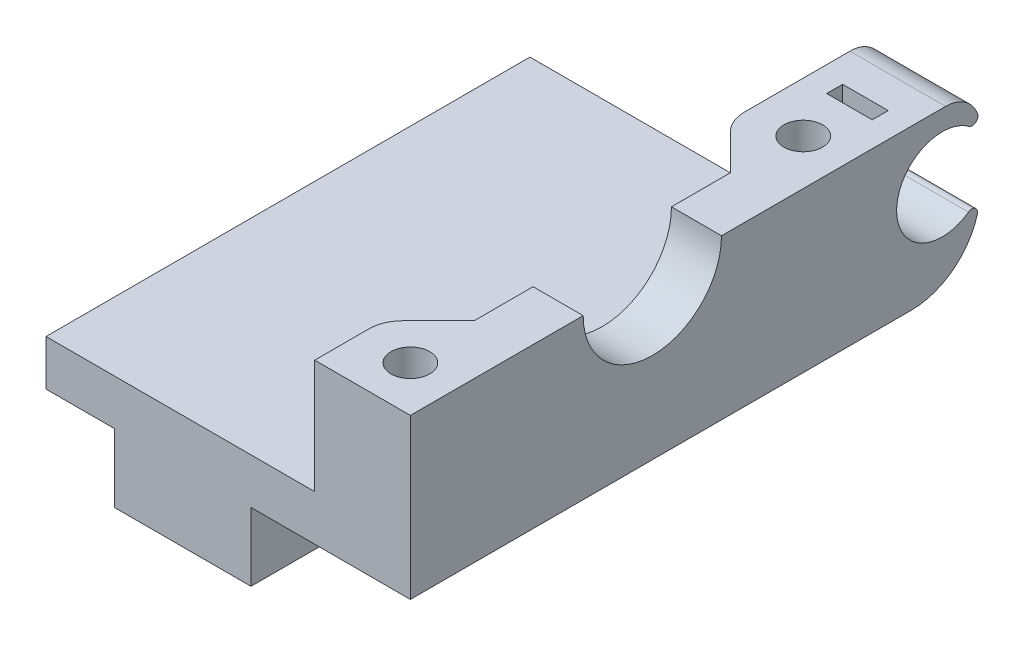
SolidWorks part; units mm, degrees
ref_plane "Plan de face" through (0, 0, 0) normal (0, 0, 1) x (1, 0, 0)
ref_plane "Plan de dessus" through (0, 0, 0) normal (0, 1, 0) x (1, 0, 0)
ref_plane "Plan de droite" through (0, 0, 0) normal (1, 0, 0) x (0, 0, -1)
sketch "Esquisse1" plane through (0, 0, 0) normal (0, 0, -1) x (1, 0, 0)
  line L0 (-1.3845, -46.2204) -> (38.6155, -46.2204)
  line L1 (38.6155, -46.2204) -> (38.6155, -42.2204)
  line L2 (38.6155, -42.2204) -> (24.6155, -42.2204)
  line L3 (24.6155, -42.2204) -> (24.6155, -36.2204)
  line L4 (24.6155, -36.2204) -> (12.6155, -36.2204)
  line L5 (12.6155, -36.2204) -> (12.6155, -42.2204)
  line L6 (12.6155, -42.2204) -> (-1.3845, -42.2204)
  line L7 (-1.3845, -42.2204) -> (-1.3845, -46.2204)
  dimension "D1" = 40
  dimension "D2" = 4
  dimension "D3" = 14
  dimension "D4" = 6
  dimension "D5" = 12
  dimension "D6" = 6
extrude "Boss.-Extru.1" add sketch "Esquisse1" along normal blind 42.5
hole_wizard "Dégagement M31" positions "Esquisse4" profile "Esquisse5" hole size "M3" standard "Din" end condition through all
sketch "Esquisse4" plane through (24.6155, 0, 0) normal (1, 0, 0) x (0, 0, -1)
  line L0 (0, 39.2204) -> (42.5, 39.2204) construction
  line L1 (0, 42.2204) -> (0, 36.2204) construction
  line L2 (42.5, 42.2204) -> (42.5, 36.2204) construction
  point P0 (10, 39.2204)
  point P2 (32.5, 39.2204)
  dimension "D1" = 10
  dimension "D2" = 10
sketch "Esquisse5" plane through (24.6155, 39.2204, -10) normal (0, 1, 0) x (0, 0, -1)
  line L0 (0, 0) -> (0, 26)
  line L1 (0, 26) -> (1.5, 26)
  line L2 (1.5, 26) -> (1.5, 0)
  line L5 (1.5, 0) -> (0, 0)
  line L11 (0, -6.35) -> (0, 107.95) construction
  dimension "Diamètre du perçage jusqu'au prochain" = 3
  dimension "Profondeur du perçage jusqu'au prochain" = 26
sketch "Esquisse10" plane through (0, 46.2204, 0) normal (0, 1, 0) x (1, 0, 0)
  line L0 (-1.3845, 0) -> (38.6155, 0) construction
  line L1 (34.2155, 0) -> (38.6155, 0)
  line L2 (34.2155, 0) -> (34.2155, 42.5)
  line L3 (34.2155, 42.5) -> (38.6155, 42.5)
  line L4 (38.6155, 0) -> (38.6155, 42.5)
  line L6 (34.2155, 42.5) -> (30.2155, 42.5)
  line L7 (34.2155, 42.5) -> (34.2155, 32.5)
  line L8 (34.2155, 32.5) -> (30.2155, 32.5)
  line L9 (30.2155, 42.5) -> (30.2155, 32.5)
  line L10 (34.2155, 0) -> (30.2155, 0)
  line L11 (34.2155, 0) -> (34.2155, 10)
  line L12 (34.2155, 10) -> (30.2155, 10)
  line L13 (30.2155, 0) -> (30.2155, 10)
  line M5 (-1.3845, 0) -> (38.6155, 0)
  line M6 (38.6155, 0) -> (38.6155, 42.5)
  line M7 (38.6155, 42.5) -> (-1.3845, 42.5)
  dimension "D1" = 4.4
  dimension "D2" = 4
  dimension "D3" = 10
  dimension "D4" = 4
  dimension "D5" = 10
extrude "Boss.-Extru.2" add sketch "Esquisse10" along normal blind 10 contours L9 L8 L2 M7 | L2 M5 M6 M7 | L13 L2 L12 M5 region at (36.4155, 46.2204, -21.25) region at (32.2155, 46.2204, -5) region at (32.2155, 46.2204, -37.5)
sketch "Esquisse12" plane through (38.6155, 0, 0) normal (1, 0, 0) x (0, 0, -1)
  line L1 (0, 56.2204) -> (42.5, 56.2204) construction
  circle A0 centre (21.25, 56.2204) radius 6.075
  dimension "D1" = 12.15
extrude "Enlèv. mat.-Extru.3" cut sketch "Esquisse12" against normal through all
hole_wizard "Dégagement M33" positions "Esquisse7" profile "Esquisse8" hole size "M3" standard "Din" end condition through all
sketch "Esquisse7" plane through (0, 42.2204, 0) normal (0, -1, 0) x (-1, 0, 0)
  line L1 (-34.6155, 38.5) -> (-2.6155, 38.5) construction
  line L2 (-34.6155, 38.5) -> (-34.6155, 4) construction
  line L3 (-34.6155, 4) -> (-2.6155, 4) construction
  line L4 (-2.6155, 38.5) -> (-2.6155, 4) construction
  line L5 (-24.6155, 42.5) -> (-12.6155, 42.5) construction
  line L6 (1.3845, 42.5) -> (1.3845, 0) construction
  line L7 (-38.6155, 42.5) -> (-38.6155, 0) construction
  point P0 (3, -59.9463)
  point P1 (-34.6155, 38.5)
  point P3 (-2.6155, 38.5)
  point P5 (-2.6155, 4)
  point P7 (-34.6155, 4)
  dimension "D1" = 4
  dimension "D2" = 4
  dimension "D3" = 4
  dimension "D4" = 4
sketch "Esquisse8" plane through (-3, 42.2204, 59.9463) normal (1, 0, 0) x (0, 0, -1)
  line L0 (0, 0) -> (0, 14)
  line L1 (0, 14) -> (1.7, 14)
  line L2 (1.7, 14) -> (1.7, 0)
  line L5 (1.7, 0) -> (0, 0)
  line L11 (0, -6.35) -> (0, 107.95) construction
  dimension "Diamètre du perçage jusqu'au prochain" = 3.4
  dimension "Profondeur du perçage jusqu'au prochain" = 14
sketch "Esquisse9" plane through (0, 42.2204, 0) normal (0, -1, 0) x (1, 0, 0)
  line L1 (32.8655, -35.4689) -> (31.1155, -38.5)
  line L2 (31.1155, -38.5) -> (32.8655, -41.5311)
  line L3 (32.8655, -41.5311) -> (36.3655, -41.5311)
  line L4 (36.3655, -41.5311) -> (38.1155, -38.5)
  line L5 (38.1155, -38.5) -> (36.3655, -35.4689)
  line L6 (36.3655, -35.4689) -> (32.8655, -35.4689)
  line L7 (4.3655, -35.4689) -> (0.8655, -35.4689)
  line L8 (0.8655, -35.4689) -> (-0.8845, -38.5)
  line L9 (-0.8845, -38.5) -> (0.8655, -41.5311)
  line L10 (0.8655, -41.5311) -> (4.3655, -41.5311)
  line L11 (4.3655, -41.5311) -> (6.1155, -38.5)
  line L12 (6.1155, -38.5) -> (4.3655, -35.4689)
  line L13 (32.8655, -0.9689) -> (31.1155, -4)
  line L14 (31.1155, -4) -> (32.8655, -7.0311)
  line L15 (32.8655, -7.0311) -> (36.3655, -7.0311)
  line L16 (36.3655, -7.0311) -> (38.1155, -4)
  line L17 (38.1155, -4) -> (36.3655, -0.9689)
  line L18 (36.3655, -0.9689) -> (32.8655, -0.9689)
  line L19 (4.3655, -0.9689) -> (0.8655, -0.9689)
  line L20 (0.8655, -0.9689) -> (-0.8845, -4)
  line L21 (-0.8845, -4) -> (0.8655, -7.0311)
  line L22 (0.8655, -7.0311) -> (4.3655, -7.0311)
  line L23 (4.3655, -7.0311) -> (6.1155, -4)
  line L24 (6.1155, -4) -> (4.3655, -0.9689)
  circle A0 centre (34.6155, -38.5) radius 3.0311 construction
  circle A1 centre (2.6155, -38.5) radius 3.0311 construction
  circle A2 centre (34.6155, -4) radius 3.0311 construction
  circle A3 centre (2.6155, -4) radius 3.0311 construction
  dimension "D1" = 3.5
extrude "Enlèv. mat.-Extru.1" cut sketch "Esquisse9" against normal blind 1.5
chamfer "Chanfrein1" distance 4 angle 45 2 edges at (30.2155, 51.2204, -32.5) (30.2155, 51.2204, -10)
sketch "Esquisse13" plane through (0, 0, -42.5) normal (0, 0, -1) x (-1, 0, 0)
  line L0 (-12.6155, 42.2204) -> (1.3845, 42.2204) construction
  line L1 (1.3845, 46.2204) -> (-6.6155, 46.2204)
  line L2 (1.3845, 46.2204) -> (1.3845, 42.2204)
  line L3 (1.3845, 42.2204) -> (-6.6155, 42.2204)
  line L4 (-6.6155, 46.2204) -> (-6.6155, 42.2204)
  line L5 (-12.6155, 36.2204) -> (-12.6155, 42.2204) construction
  dimension "D1" = 6
extrude "Enlèv. mat.-Extru.4" cut sketch "Esquisse13" against normal through all
sketch "Esquisse14" plane through (0, 0, -42.5) normal (0, 0, -1) x (-1, 0, 0)
  line L1 (-30.2155, 56.2204) -> (-38.6155, 56.2204)
  line L2 (-30.2155, 56.2204) -> (-30.2155, 42.2204)
  line L3 (-30.2155, 42.2204) -> (-38.6155, 42.2204)
  line L4 (-38.6155, 56.2204) -> (-38.6155, 42.2204)
extrude "Boss.-Extru.3" add sketch "Esquisse14" along normal blind 7.5
sketch "Esquisse15" plane through (30.2155, 0, 0) normal (-1, 0, 0) x (0, 0, 1)
  line L0 (-50, 42.2204) -> (-50, 56.2204) construction
  circle A0 centre (-46.7, 50.4385) radius 4
  dimension "D1" = 8
  dimension "D2" = 3.3
extrude "Enlèv. mat.-Extru.5" cut sketch "Esquisse15" against normal through all
fillet "Congé2" radius 3 1 edges at (34.4155, 56.2204, -50)
fillet "Congé3" radius 6 1 edges at (34.4155, 42.2204, -50)
fillet "Congé4" radius 0.5 2 edges at (34.4155, 52.699, -50) (34.4155, 48.1779, -50)
sketch "Esquisse16" plane through (0, 56.2204, 0) normal (0, 1, 0) x (1, 0, 0)
  line L0 (34.4155, 44.1603) -> (34.4155, 49.8188) construction
  line L1 (32.4155, 44.1603) -> (36.4155, 44.1603)
  line L2 (32.4155, 44.1603) -> (32.4155, 42.7603)
  line L3 (32.4155, 42.7603) -> (36.4155, 42.7603)
  line L4 (36.4155, 44.1603) -> (36.4155, 42.7603)
  line L5 (38.6155, 49.8188) -> (30.2155, 49.8188) construction
  dimension "D1" = 1.4
  dimension "D2" = 4
extrude "Enlèv. mat.-Extru.6" cut sketch "Esquisse16" against normal through all
fillet "Congé5" radius 3 2 edges at (30.2155, 51.2204, -6) (30.2155, 51.2204, -36.5)
